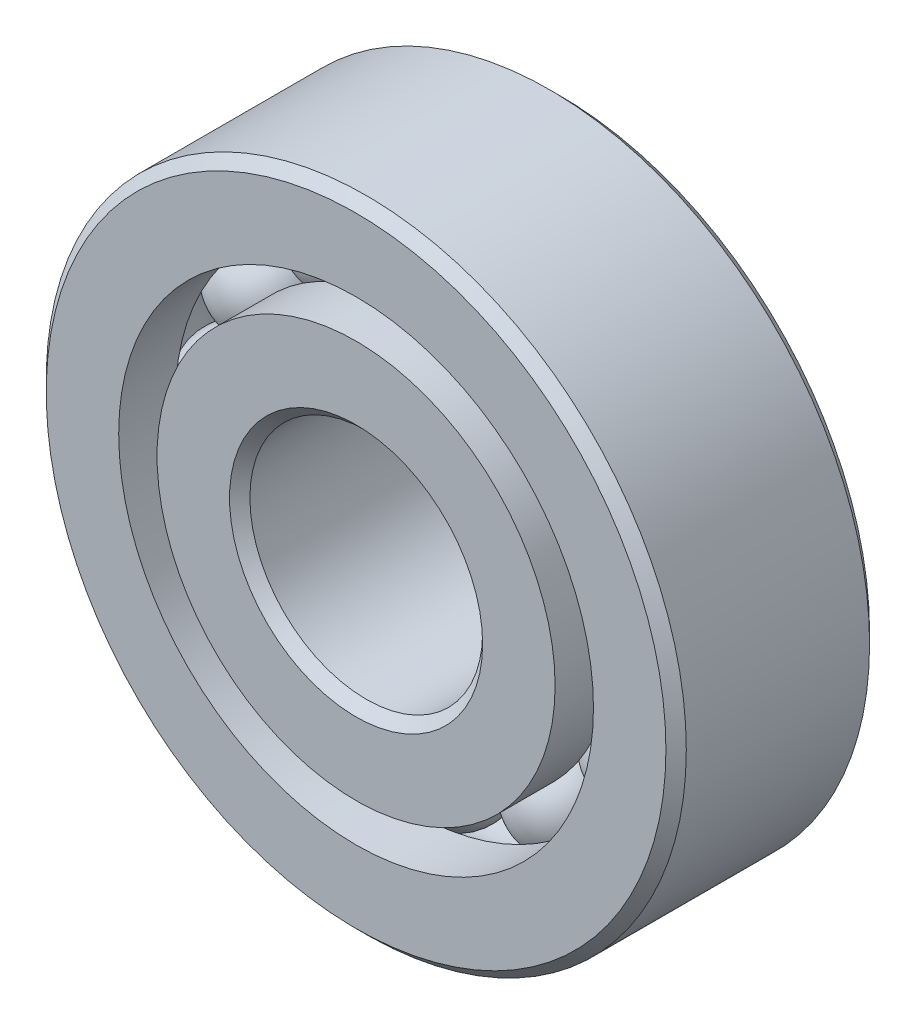
SolidWorks part; units mm, degrees
ref_plane "Front Plane" through (0, 0, 0) normal (0, 0, 1) x (1, 0, 0)
ref_plane "Top Plane" through (0, 0, 0) normal (0, 1, 0) x (1, 0, 0)
ref_plane "Right Plane" through (0, 0, 0) normal (1, 0, 0) x (0, 0, -1)
sketch "Sketch1" plane through (0, 0, 0) normal (1, 0, 0) x (0, 0, -1)
  line L0 (-3.5, 0) -> (3.5, 0) construction
  line L1 (0, 11) -> (0, -11) construction
  line L2 (3.15, 11) -> (-3.15, 11)
  line L3 (-3.15, 11) -> (-3.5, 10.65)
  line L4 (-3.5, 10.65) -> (-3.5, 8.1593)
  line L5 (-3.5, 8.1593) -> (-1.5556, 8.1593)
  line L6 (3.5, 8.1593) -> (1.5556, 8.1593)
  line L7 (3.5, 10.65) -> (3.5, 8.1593)
  line L8 (3.15, 11) -> (3.5, 10.65)
  line L9 (0, 11) -> (0, 7.5) construction
  line L10 (0, 7.5) -> (0, 4) construction
  arc A0 (-1.5556, 8.1593) -> (1.5556, 8.1593) centre (0, 7.5) cw
  point P14 (0, 4)
  dimension "Width" = 7
  dimension "OD" = 22
  dimension "D1" = 45
  dimension "D2" = 0.35
  dimension "Shaft Dia" = 8
  dimension "D3" = 3.1111
  dimension "D4" = 0.6593
revolve "Revolve1" add sketch "Sketch1" angle 360 about L0
sketch "Sketch3" plane through (0, 0, 0) normal (1, 0, 0) x (0, 0, -1)
  line L0 (-3.5, 6.8407) -> (-1.5556, 6.8407)
  line L1 (0, 11) -> (0, -11) construction
  line L2 (-3.5, 10.65) -> (-3.5, 8.1593) construction
  line L3 (-3.5, 6.8407) -> (-3.5, 4.35)
  line L4 (-3.15, 11) -> (-3.5, 10.65) construction
  line L5 (-3.5, 4.35) -> (-3.15, 4)
  line L6 (-3.15, 4) -> (3.15, 4)
  line L7 (3.15, 11) -> (3.15, -11) construction
  line L8 (3.15, 4) -> (3.5, 4.35)
  line L9 (3.5, -10.65) -> (3.5, 10.65) construction
  line L10 (3.5, 4.35) -> (3.5, 6.8407)
  line L11 (3.5, 6.8407) -> (1.5556, 6.8407)
  line L13 (3.15, 11) -> (3.5, 10.65) construction
  arc A0 (1.5556, 8.1593) -> (-1.5556, 8.1593) centre (0, 7.5) ccw construction
  arc A1 (1.5556, 6.8407) -> (-1.5556, 6.8407) centre (0, 7.5) cw
revolve "Revolve3" add sketch "Sketch3" angle 360 about L0
sketch "Sketch4" plane through (0, 0, 0) normal (1, 0, 0) x (0, 0, -1)
  line L0 (-1.6895, 7.5) -> (1.6895, 7.5)
  arc A2 (-1.6895, 7.5) -> (1.6895, 7.5) centre (0, 7.5) cw
  arc A3 (1.5556, 8.1593) -> (-1.5556, 8.1593) centre (0, 7.5) ccw construction
revolve "Revolve4" add sketch "Sketch4" angle 360 about L0
ref_axis "Axis1" through (0, 0, -3.5) along (0, 0, 1)
pattern_circular "CirPattern1" count 12 every 30 about axis through (0, 0, -3.5) along (0, 0, 1) of bodies 104
sketch "Sketch5" plane through (0, 0, 0) normal (1, 0, 0) x (0, 0, -1)
  line L0 (-3.5, 8.1593) -> (-1.5556, 8.1593) construction
  line L1 (-3.325, 8.1593) -> (-1.6895, 8.1593)
  line L2 (-3.325, 8.1593) -> (-3.325, 6.8407)
  line L3 (-3.325, 6.8407) -> (-1.6895, 6.8407)
  line L4 (-1.6895, 8.1593) -> (-1.6895, 6.8407)
  line L5 (-3.5, 6.8407) -> (-1.5556, 6.8407) construction
  line L6 (3.5, 8.1593) -> (1.5556, 8.1593) construction
  line L7 (3.325, 8.1593) -> (1.6895, 8.1593)
  line L8 (3.325, 8.1593) -> (3.325, 6.8407)
  line L9 (3.325, 6.8407) -> (1.6895, 6.8407)
  line L10 (1.6895, 8.1593) -> (1.6895, 6.8407)
  line L11 (3.5, 6.8407) -> (1.5556, 6.8407) construction
  line L12 (-3.15, 11) -> (-3.5, 10.65) construction
  point P18 (-3.325, 10.825)
sketch "Sketch6" plane through (0, 0, -3.5) normal (0, 0, -1) x (-1, 0, 0)
  line L0 (10.65, 0) -> (-10.65, 0) construction
  line L2 (0, 10.65) -> (0, -10.65) construction
  circle A0 centre (0, 0) radius 10.65 construction
equation "\"D2@Sketch1\" = \"Width@Sketch1\"*.05"
equation "\"D3@Sketch1\" = \"Width@Sketch1\"/2.25"
equation "\"D4@Sketch1\" = (((\"OD@Sketch1\"-\"Width@Sketch1\")/2)/3.25)/3.5"
equation "\"D2@CirPattern1\" = 360/\"Balls@CirPattern1\""
